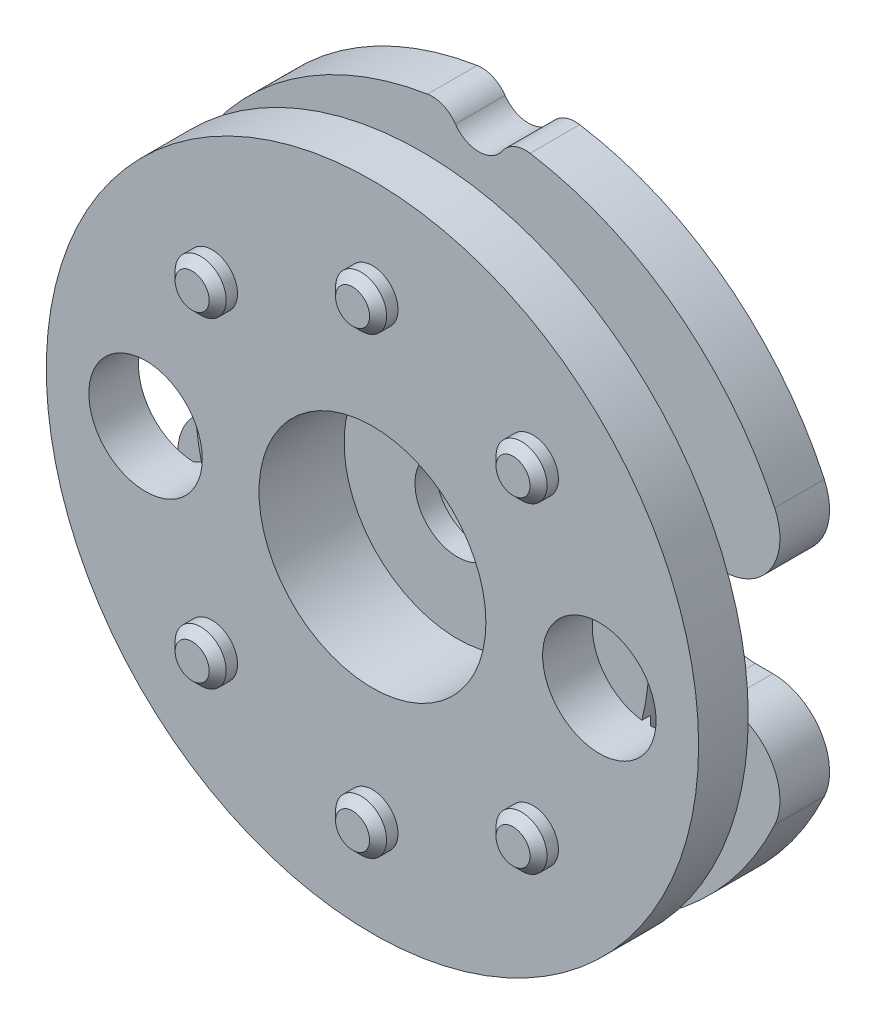
SolidWorks part; units mm, degrees
ref_plane "前视基准面" through (0, 0, 0) normal (0, 0, 1) x (1, 0, 0)
ref_plane "上视基准面" through (0, 0, 0) normal (0, 1, 0) x (1, 0, 0)
ref_plane "右视基准面" through (0, 0, 0) normal (1, 0, 0) x (0, 0, -1)
sketch "草图1" plane through (0, 0, 0) normal (0, 0, 1) x (1, 0, 0)
  circle A0 centre (0, 0) radius 11.5
extrude "凸台-拉伸1" add sketch "草图1" along normal mid plane 5.5
sketch "草图2" plane through (0, 0, 0) normal (0, 0, 1) x (1, 0, 0)
  circle A0 centre (0, 0) radius 11.5
  circle A2 centre (0, 0) radius 8
extrude "切除-拉伸1" cut sketch "草图2" against normal mid plane 2
sketch "草图3" plane through (0, 0, 2.75) normal (0, 0, 1) x (1, 0, 0)
  circle A0 centre (0, 0) radius 1.5
extrude "切除-拉伸2" cut sketch "草图3" against normal through all
sketch "草图5" plane through (0, 0, -2.75) normal (0, 0, -1) x (-1, 0, 0)
  circle A0 centre (0, 0) radius 2.75
extrude "切除-拉伸4" cut sketch "草图5" against normal blind 2
sketch "草图6" plane through (0, 0, 2.75) normal (0, 0, 1) x (1, 0, 0)
  circle A0 centre (0, 0) radius 8
  circle A1 centre (-8, 0) radius 2
  circle A2 centre (8, 0) radius 2
extrude "切除-拉伸5" cut sketch "草图6" against normal through all contours A0 A1 | A0 A1 | A0 A2 | A0 A2 region at (7.1078, 0, 2.75) region at (8.8022, 0, 2.75) region at (-7.1078, 0, 2.75) region at (-8.8022, 0, 2.75)
sketch "草图7" plane through (0, 0, -2.75) normal (0, 0, -1) x (-1, 0, 0)
  line L0 (-8, -2) -> (-11.3248, -2)
  line L1 (-8, 2) -> (-11.3248, 2)
  line L2 (0, 4.5319) -> (0, -5.3257) construction
  line L3 (8, 2) -> (11.3248, 2)
  line L4 (8, -2) -> (11.3248, -2)
  arc A0 (-8, 2) -> (-8, -2) centre (-8, 0) cw
  circle A1 centre (-8, 0) radius 2 construction
  circle A2 centre (0, 0) radius 11.5 construction
  arc A3 (-11.3248, 2) -> (-11.2457, -2.4048) centre (0, 0) ccw
  arc A4 (11.3248, 2) -> (11.2457, -2.4048) centre (0, 0) cw
  arc A5 (8, 2) -> (8, -2) centre (8, 0) ccw
  circle M4 centre (-8, 0) radius 2
  circle M5 centre (8, 0) radius 2
  circle M7 centre (0, 0) radius 11.5
extrude "切除-拉伸6" cut sketch "草图7" against normal up to next contours L1 L0 M4 M7 | L4 L3 M5 M7 region at (10.4538, 0, -2.75) region at (-10.4538, 0, -2.75)
sketch "草图10" plane through (0, 0, -2.75) normal (0, 0, -1) x (-1, 0, 0)
  line L0 (0, 11.5) -> (0, -11.5) construction
  arc A2 (11.3248, 2) -> (-11.3248, 2) centre (0, 0) ccw construction
  arc A3 (-11.3248, -2) -> (11.3248, -2) centre (0, 0) ccw construction
  circle A4 centre (0, 8) radius 1
  circle A5 centre (0, 11.5) radius 1
  circle A6 centre (0, -8) radius 1
  circle A7 centre (0, -11.5) radius 1
extrude "切除-拉伸14" cut sketch "草图10" against normal up to surface (1.75 mm away) up to face at (0, -4.582, -1)
fillet "圆角1" radius 2 4 edges at (11.3248, -2, -1.875) (11.3248, 2, -1.875) (-11.3248, -2, -1.875) (-11.3248, 2, -1.875)
fillet "圆角2" radius 1 4 edges at (-0.9991, -11.4565, -1.875) (0.9991, -11.4565, -1.875) (-0.9991, 11.4565, -1.875) (0.9991, 11.4565, -1.875)
sketch "草图11" plane through (0, 0, 2.75) normal (0, 0, 1) x (1, 0, 0)
  circle A1 centre (0, 8) radius 0.9
  circle A2 centre (-5.6569, 5.6569) radius 0.9
  circle A3 centre (5.6569, 5.6569) radius 0.9
  circle A4 centre (0, -8) radius 0.9
  circle A5 centre (-5.6569, -5.6569) radius 0.9
  circle A6 centre (5.6569, -5.6569) radius 0.9
extrude "凸台-拉伸2" add sketch "草图11" along normal blind 0.7
chamfer "倒角2" distance 0.3 angle 45 6 edges at (-4.7569, -5.6569, 3.45) (0.9, -8, 3.45) (6.5569, -5.6569, 3.45) (6.5569, 5.6569, 3.45) (0.9, 8, 3.45) (-4.7569, 5.6569, 3.45)
sketch "草图12" plane through (0, 0, 1) normal (0, 0, -1) x (-1, 0, 0)
  circle A0 centre (0, 0) radius 8
extrude "凸台-拉伸3" add sketch "草图12" along normal up to surface (2 mm away) up to face at (0, -6.1621, -1)
chamfer "倒角3" distance 0.3 angle 45 6 edges at (0, -8, 1) (0, 8, 1) (5.2908, 6.0007, -1) (-5.2908, -6.0007, -1) (5.2908, -6.0007, -1) (-5.2908, 6.0007, -1)
sketch "草图13" plane through (0, 0, 2.75) normal (0, 0, 1) x (1, 0, 0)
  circle A0 centre (0, 0) radius 4
extrude "切除-拉伸15" cut sketch "草图13" against normal blind 3
sketch "草图14" plane through (0, 0, -0.25) normal (0, 0, 1) x (1, 0, 0)
  circle A0 centre (0, 0) radius 1.5
  dimension "D1" = 3
extrude "切除-拉伸16" cut sketch "草图14" against normal through all
